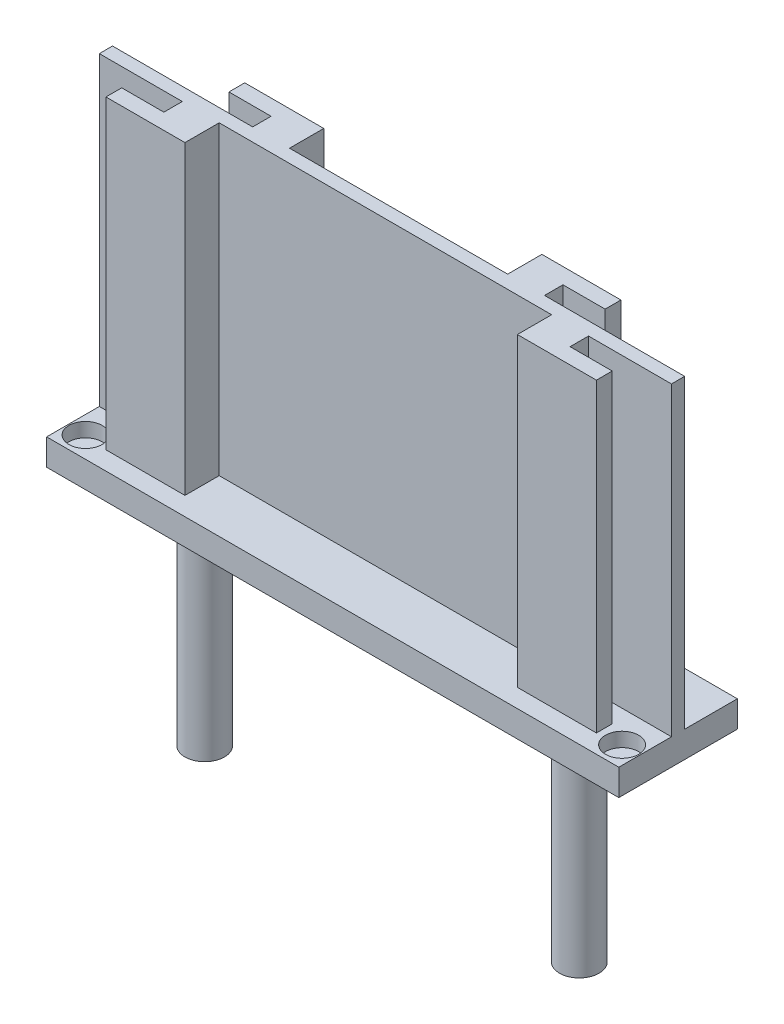
SolidWorks part; units mm, degrees
ref_plane "Front Plane" through (0, 0, 0) normal (0, 0, 1) x (1, 0, 0)
ref_plane "Top Plane" through (0, 0, 0) normal (0, 1, 0) x (1, 0, 0)
ref_plane "Right Plane" through (0, 0, 0) normal (1, 0, 0) x (0, 0, -1)
sketch "Sketch1" plane through (0, 0, 0) normal (0, 1, 0) x (1, 0, 0)
  line L1 (-54.3, -11.25) -> (54.3, -11.25)
  line L2 (-54.3, -11.25) -> (-54.3, 11.25)
  line L3 (-54.3, 11.25) -> (54.3, 11.25)
  line L4 (54.3, -11.25) -> (54.3, 11.25)
  line L5 (-54.3, -11.25) -> (54.3, 11.25) construction
  line L6 (-54.3, 11.25) -> (54.3, -11.25) construction
  point P0 (0, 0)
  dimension "D1" = 108.6
  dimension "D2" = 22.5
extrude "Boss-Extrude1" add sketch "Sketch1" along normal blind 5
sketch "Sketch2" plane through (0, 5, 0) normal (0, 1, 0) x (1, 0, 0)
  line L0 (-54.3, -11.25) -> (54.3, -11.25) construction
  line L2 (54.3, 11.25) -> (-54.3, 11.25) construction
  line L3 (0, 11.25) -> (0, -11.25) construction
  circle A4 centre (50.925, -7.25) radius 3.15 construction
  circle A5 centre (40.075, 7.25) radius 3.15 construction
  circle A6 centre (-50.925, -7.25) radius 3.15 construction
  circle A7 centre (-40.075, 7.25) radius 3.15 construction
  circle A8 centre (50.925, -7.25) radius 3.15
  circle A9 centre (40.075, 7.25) radius 3.15
  circle A10 centre (-50.925, -7.25) radius 3.15
  circle A11 centre (-40.075, 7.25) radius 3.15
extrude "Cut-Extrude1" cut sketch "Sketch2" against normal blind 2.7
sketch "Sketch3" plane through (0, 5, 0) normal (0, 1, 0) x (1, 0, 0)
  line L0 (-54.3, 0) -> (54.3, 0) construction
  line L1 (-54.3, 11.25) -> (-54.3, -11.25) construction
  line L2 (54.3, -11.25) -> (54.3, 11.25) construction
  line L3 (-38.55, -1.25) -> (-38.55, -4.75)
  line L4 (-54.3, 1.25) -> (54.3, 1.25)
  line L5 (-54.3, 1.25) -> (-54.3, -1.25)
  line L6 (-54.3, -1.25) -> (54.3, -1.25)
  line L7 (54.3, 1.25) -> (54.3, -1.25)
  line L8 (-38.55, -4.75) -> (-46.55, -4.75)
  line L9 (-46.55, -4.75) -> (-46.55, -7.75)
  line L14 (-46.55, -7.75) -> (-31.55, -7.75)
  line L15 (-31.55, -7.75) -> (-31.55, -1.25)
  line L16 (-38.55, -1.25) -> (-31.55, -1.25)
  line L17 (-27.7, 1.25) -> (-27.7, 4.75)
  line L18 (-27.7, 4.75) -> (-35.7, 4.75)
  line L19 (-35.7, 4.75) -> (-35.7, 7.75)
  line L24 (-35.7, 7.75) -> (-20.7, 7.75)
  line L25 (-20.7, 7.75) -> (-20.7, 1.25)
  line L26 (-27.7, 1.25) -> (-20.7, 1.25)
  point P10 (-54.3, 0)
  line M20 (54.3, -11.25) -> (54.3, 11.25)
  line M22 (-54.3, 11.25) -> (-54.3, -11.25)
  dimension "D1" = 2.5
  dimension "D2" = 3
  dimension "D3" = 8
  dimension "D4" = 7.75
  dimension "D5" = 3.5
  dimension "D7" = 22.75
  dimension "D10" = 3.5
  dimension "D11" = 3
  dimension "D12" = 18.6
  dimension "D13" = 33.6
  dimension "D16" = 8
extrude "Boss-Extrude2" add sketch "Sketch3" along normal blind 58 contours L0 L7 L4 M22 | L0 L5 L6 M20 | L14 L15 L6 L3 L8 L9 | L25 L24 L19 L18 L17 L4 region at (0, 5, -0.625) region at (0, 5, 0.625) region at (-26.7899, 5, -5.1043) region at (-37.6399, 5, 5.1043)
ref_plane "Plane1" through (0, 0, 0) normal (1, 0, 0) x (0, 0, -1)
mirror "Mirror1" about plane through (0, 0, 0) normal (1, 0, 0) of "Boss-Extrude2"
sketch "Sketch4" plane through (0, 0, 0) normal (0, -1, 0) x (1, 0, 0)
  line L0 (-54.3, -11.25) -> (-54.3, 11.25) construction
  line L2 (54.3, 11.25) -> (54.3, -11.25) construction
  circle A0 centre (-35.55, 0) radius 1.5
  circle A1 centre (35.55, 0) radius 1.5
  circle A2 centre (-35.55, 0) radius 3.75
  circle A3 centre (35.55, 0) radius 3.75
  dimension "D3" = 3
  dimension "D4" = 3
  dimension "D5" = 7.5
  dimension "D6" = 7.5
  dimension "D1" = 18.75
  dimension "D2" = 18.75
  dimension "D7" = 71.1
extrude "Boss-Extrude3" add sketch "Sketch4" along normal blind 42
fillet "Fillet1" radius 1 2 edges at (35.55, 0, -3.75) (-35.55, 0, -3.75)
